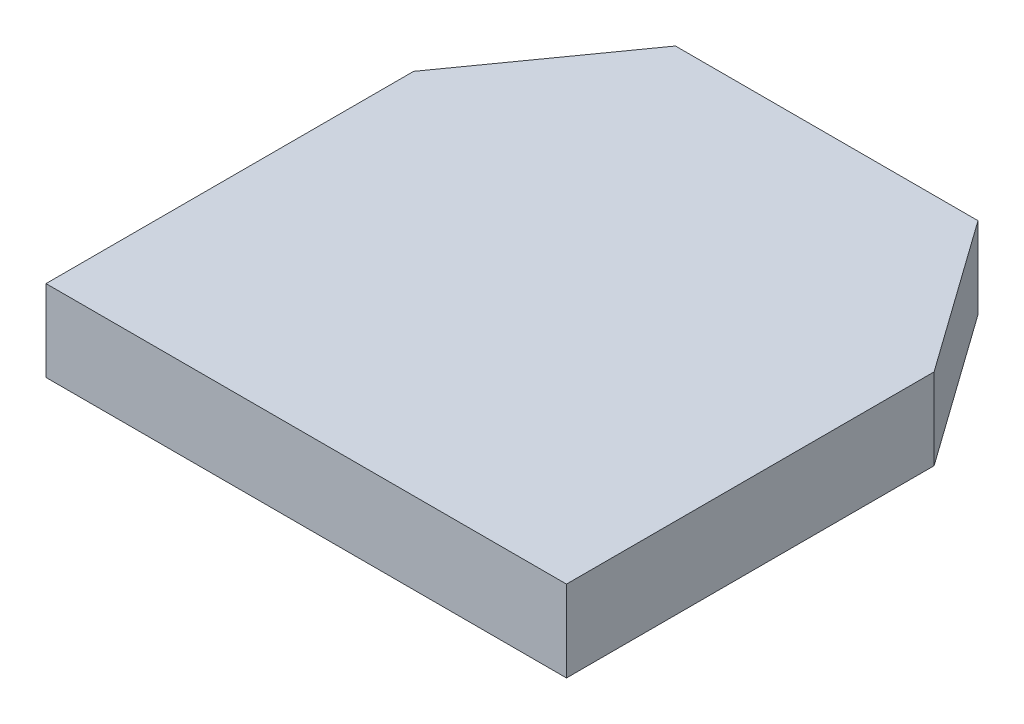
SolidWorks part; units mm, degrees
ref_plane "Front Plane" through (0, 0, 0) normal (0, 0, 1) x (1, 0, 0)
ref_plane "Top Plane" through (0, 0, 0) normal (0, 1, 0) x (1, 0, 0)
ref_plane "Right Plane" through (0, 0, 0) normal (1, 0, 0) x (0, 0, -1)
sketch "Sketch1" plane through (0, 0, 0) normal (0, 1, 0) x (1, 0, 0)
  line L0 (0, 28.702) -> (8.509, 40.64)
  line L1 (0, 0) -> (40.64, 0)
  line L2 (0, 0) -> (0, 28.702)
  line L3 (8.509, 40.64) -> (32.131, 40.64)
  line L4 (40.64, 0) -> (40.64, 28.702)
  line L5 (40.64, 28.702) -> (32.131, 40.64)
  point P1 (40.64, 40.64)
  point P2 (0, 40.64)
  dimension "D1" = 40.64
  dimension "D2" = 40.64
  dimension "D3" = 11.938
  dimension "D4" = 8.509
  dimension "D5" = 11.938
  dimension "D6" = 8.509
extrude "Boss-Extrude1" add sketch "Sketch1" along normal blind 6.35
ref_plane "Plane1" through (20.32, 0, 0) normal (1, 0, 0) x (0, 0, -1)
ref_plane "Plane2" through (0, 3.175, 0) normal (0, -1, 0) x (-1, 0, 0)
